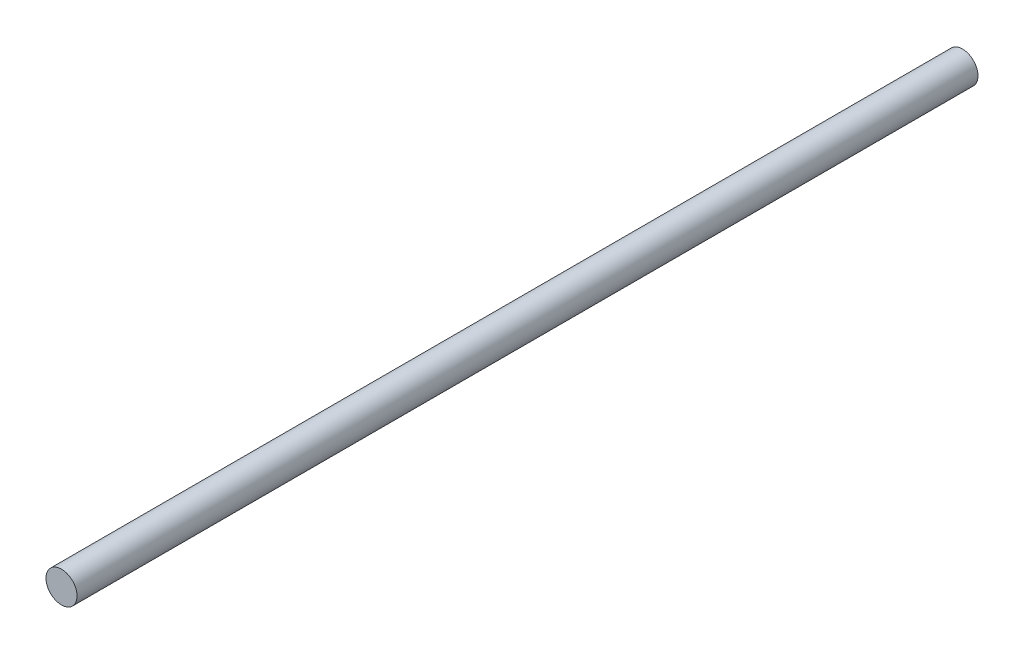
SolidWorks part; units mm, degrees
material "Rubber"
ref_plane "Front Plane" through (0, 0, 0) normal (0, 0, 1) x (1, 0, 0)
ref_plane "Top Plane" through (0, 0, 0) normal (0, 1, 0) x (1, 0, 0)
ref_plane "Right Plane" through (0, 0, 0) normal (1, 0, 0) x (0, 0, -1)
sketch "Sketch1" plane through (0, 0, 0) normal (0, 0, 1) x (1, 0, 0)
  circle A0 centre (0, 0) radius 12.7
  dimension "D1" = 25.4
extrude "Boss-Extrude1" add sketch "Sketch1" along normal blind 736.6
